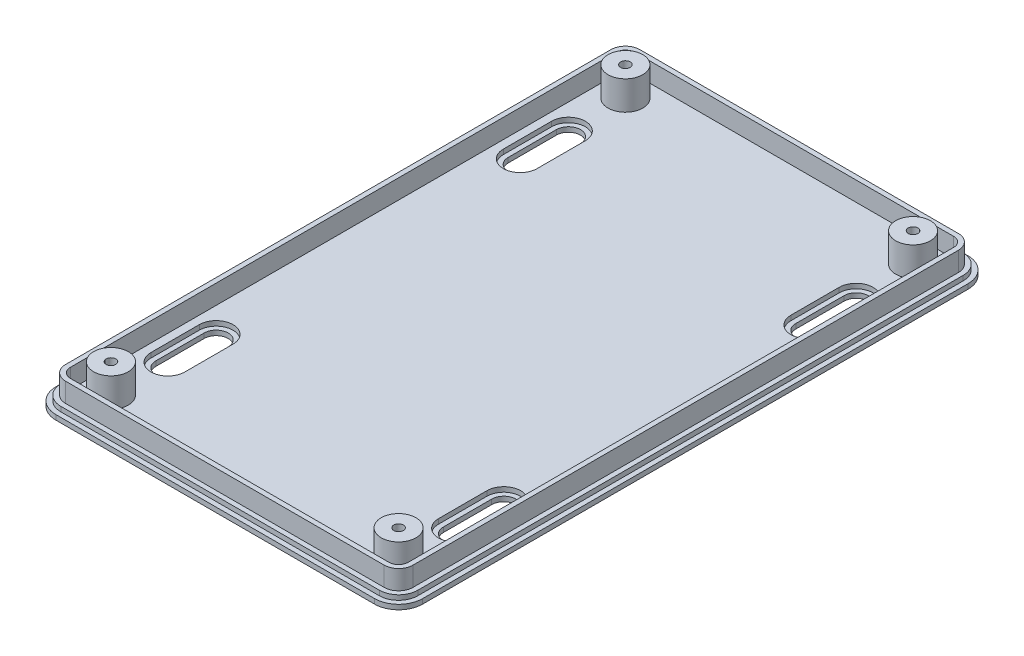
SolidWorks part; units mm, degrees
material "ABS"
ref_plane "Front Plane" through (0, 0, 0) normal (0, 0, 1) x (1, 0, 0)
ref_plane "Top Plane" through (0, 0, 0) normal (0, 1, 0) x (1, 0, 0)
ref_plane "Right Plane" through (0, 0, 0) normal (1, 0, 0) x (0, 0, -1)
sketch "Sketch1" plane through (0, 0, 0) normal (0, 1, 0) x (1, 0, 0)
  line L1 (-33, -56.5) -> (33, -56.5) construction
  line L2 (-33, -56.5) -> (-33, 56.5) construction
  line L3 (-33, 56.5) -> (33, 56.5) construction
  line L4 (33, -56.5) -> (33, 56.5) construction
  line L5 (-33, -56.5) -> (33, 56.5) construction
  line L6 (-33, 56.5) -> (33, -56.5) construction
  line L7 (-38, -61.5) -> (38, -61.5)
  line L8 (-38, -61.5) -> (-38, 61.5)
  line L9 (-38, 61.5) -> (38, 61.5)
  line L10 (38, -61.5) -> (38, 61.5)
  line L11 (-38, -61.5) -> (38, 61.5) construction
  line L12 (-38, 61.5) -> (38, -61.5) construction
  circle A0 centre (-29.8, 53.3) radius 3.6
  circle A1 centre (29.8, 53.3) radius 3.6
  circle A2 centre (29.8, -53.3) radius 3.6
  circle A3 centre (-29.8, -53.3) radius 3.6
  point P0 (0, 0)
  point P14 (0, 0)
  dimension "D5" = 7.2
  dimension "D6" = 7.2
  dimension "D7" = 7.2
  dimension "D8" = 7.2
  dimension "D1" = 66
  dimension "D2" = 113
  dimension "D3" = 3.2
  dimension "D4" = 3.2
  dimension "D9" = 3.2
  dimension "D10" = 3.2
  dimension "D11" = 3.2
  dimension "D12" = 3.2
  dimension "D13" = 3.2
  dimension "D14" = 3.2
  dimension "D15" = 5
  dimension "D16" = 5
extrude "Boss-Extrude2" add sketch "Sketch1" against normal blind 2 contours A3 | L7 L10 L9 L8 A3 A2 A1 A0 | A2 | A0 | A1 | A3 | L8 L7 L10 L9 region at (0, 0, 0) region at (-29.8, 0, -53.3) region at (29.8, 0, -53.3) region at (29.8, 0, 53.3) region at (-29.8, 0, 53.3)
extrude "Boss-Extrude3" add sketch "Sketch1<4>" along normal blind 6 contours A3 | A2 | A0 | A1 region at (-29.8, 0, -53.3) region at (29.8, 0, -53.3) region at (29.8, 0, 53.3) region at (-29.8, 0, 53.3)
sketch "Sketch1<4>" plane through (0, 0, 0) normal (0, 1, 0) x (1, 0, 0) same geometry as "Sketch1"
fillet "Fillet1" radius 5 4 edges at (-38, -1, -61.5) (38, -1, -61.5) (38, -1, 61.5) (-38, -1, 61.5)
sketch "Sketch2" plane through (0, 0, 0) normal (0, 1, 0) x (1, 0, 0)
  line L0 (-29.8, 41.5) -> (-29.8, 31.5) construction
  line L1 (-27.3, 41.5) -> (-27.3, 31.5)
  line L2 (-32.3, 41.5) -> (-32.3, 31.5)
  line L3 (-38, -56.5) -> (-38, 56.5) construction
  line L4 (-33, 61.5) -> (33, 61.5) construction
  line L5 (0, 0) -> (0, 31.5) construction
  line L6 (0, 0) -> (35.6164, 0) construction
  line L7 (29.8, 41.5) -> (29.8, 31.5) construction
  line L8 (27.3, 41.5) -> (27.3, 31.5)
  line L9 (32.3, 41.5) -> (32.3, 31.5)
  line L10 (-29.8, -41.5) -> (-29.8, -31.5) construction
  line L11 (-27.3, -41.5) -> (-27.3, -31.5)
  line L12 (-32.3, -41.5) -> (-32.3, -31.5)
  line L13 (29.8, -41.5) -> (29.8, -31.5) construction
  line L14 (27.3, -41.5) -> (27.3, -31.5)
  line L15 (32.3, -41.5) -> (32.3, -31.5)
  arc A0 (-27.3, 41.5) -> (-32.3, 41.5) centre (-29.8, 41.5) ccw
  arc A1 (-32.3, 31.5) -> (-27.3, 31.5) centre (-29.8, 31.5) ccw
  arc A2 (27.3, 41.5) -> (32.3, 41.5) centre (29.8, 41.5) cw
  arc A3 (32.3, 31.5) -> (27.3, 31.5) centre (29.8, 31.5) cw
  arc A4 (-27.3, -41.5) -> (-32.3, -41.5) centre (-29.8, -41.5) cw
  arc A5 (-32.3, -31.5) -> (-27.3, -31.5) centre (-29.8, -31.5) cw
  arc A6 (27.3, -41.5) -> (32.3, -41.5) centre (29.8, -41.5) ccw
  arc A7 (32.3, -31.5) -> (27.3, -31.5) centre (29.8, -31.5) ccw
  point P2 (-29.8, 36.5)
  point P17 (29.8, 36.5)
  point P24 (-29.8, -36.5)
  point P31 (29.8, -36.5)
  dimension "D1" = 2.5
  dimension "D2" = 10
  dimension "D3" = 8.2
  dimension "D4" = 20
extrude "Cut-Extrude1" cut sketch "Sketch2" against normal through all
sketch "Sketch3" plane through (0, 6, 0) normal (0, 1, 0) x (1, 0, 0)
  line L0 (0, 0) -> (0, -21.6233) construction
  line L1 (0, 0) -> (38, 0) construction
  line L2 (38, -56.5) -> (38, 56.5) construction
  circle A0 centre (-29.8, -53.3) radius 1
  circle A1 centre (29.8, -53.3) radius 1
  circle A2 centre (29.8, 53.3) radius 1
  circle A3 centre (-29.8, 53.3) radius 1
  dimension "D1" = 2
extrude "Cut-Extrude2" cut sketch "Sketch3" against normal through all
sketch "Sketch4" plane through (0, 0, 0) normal (0, 1, 0) x (1, 0, 0)
  line L0 (-33, -61.5) -> (33, -61.5) construction
  line L1 (-38, -56.5) -> (-38, 56.5) construction
  line L2 (-33, 61.5) -> (33, 61.5) construction
  line L3 (38, -56.5) -> (38, 56.5) construction
  line L4 (-33, -61.5) -> (33, -61.5)
  line L5 (-38, -56.5) -> (-38, 56.5)
  line L6 (-33, 61.5) -> (33, 61.5)
  line L7 (38, -56.5) -> (38, 56.5)
  line L8 (-33, -60.5) -> (33, -60.5)
  line L9 (37, -56.5) -> (37, 56.5)
  line L10 (-33, 60.5) -> (33, 60.5)
  line L11 (-37, -56.5) -> (-37, 56.5)
  line L12 (27.3, -31.5) -> (27.3, -41.5) construction
  line L13 (32.3, -41.5) -> (32.3, -31.5) construction
  line L14 (-27.3, -41.5) -> (-27.3, -31.5) construction
  line L15 (-32.3, -31.5) -> (-32.3, -41.5) construction
  line L16 (-32.3, 41.5) -> (-32.3, 31.5) construction
  line L17 (-27.3, 31.5) -> (-27.3, 41.5) construction
  line L18 (27.3, 41.5) -> (27.3, 31.5) construction
  line L19 (32.3, 31.5) -> (32.3, 41.5) construction
  line L20 (32.3, 31.5) -> (32.3, 41.5)
  line L21 (27.3, 41.5) -> (27.3, 31.5)
  line L22 (-27.3, 31.5) -> (-27.3, 41.5)
  line L23 (-32.3, 41.5) -> (-32.3, 31.5)
  line L24 (-32.3, -31.5) -> (-32.3, -41.5)
  line L25 (-27.3, -41.5) -> (-27.3, -31.5)
  line L26 (32.3, -41.5) -> (32.3, -31.5)
  line L27 (27.3, -31.5) -> (27.3, -41.5)
  line L28 (33.3, 31.5) -> (33.3, 41.5)
  line L29 (26.3, 41.5) -> (26.3, 31.5)
  line L30 (-26.3, 31.5) -> (-26.3, 41.5)
  line L31 (-33.3, 41.5) -> (-33.3, 31.5)
  line L32 (-33.3, -31.5) -> (-33.3, -41.5)
  line L33 (-26.3, -41.5) -> (-26.3, -31.5)
  line L34 (33.3, -41.5) -> (33.3, -31.5)
  line L35 (26.3, -31.5) -> (26.3, -41.5)
  arc A0 (33, -61.5) -> (38, -56.5) centre (33, -56.5) ccw construction
  arc A1 (-38, -56.5) -> (-33, -61.5) centre (-33, -56.5) ccw construction
  arc A2 (-33, 61.5) -> (-38, 56.5) centre (-33, 56.5) ccw construction
  arc A3 (38, 56.5) -> (33, 61.5) centre (33, 56.5) ccw construction
  arc A4 (33, -61.5) -> (38, -56.5) centre (33, -56.5) ccw
  arc A5 (-38, -56.5) -> (-33, -61.5) centre (-33, -56.5) ccw
  arc A6 (-33, 61.5) -> (-38, 56.5) centre (-33, 56.5) ccw
  arc A7 (38, 56.5) -> (33, 61.5) centre (33, 56.5) ccw
  arc A8 (33, -60.5) -> (37, -56.5) centre (33, -56.5) ccw
  arc A9 (37, 56.5) -> (33, 60.5) centre (33, 56.5) ccw
  arc A10 (-33, 60.5) -> (-37, 56.5) centre (-33, 56.5) ccw
  arc A11 (-37, -56.5) -> (-33, -60.5) centre (-33, -56.5) ccw
  arc A12 (32.3, -31.5) -> (27.3, -31.5) centre (29.8, -31.5) ccw construction
  arc A13 (27.3, -41.5) -> (32.3, -41.5) centre (29.8, -41.5) ccw construction
  arc A14 (-32.3, -41.5) -> (-27.3, -41.5) centre (-29.8, -41.5) ccw construction
  arc A15 (-27.3, -31.5) -> (-32.3, -31.5) centre (-29.8, -31.5) ccw construction
  arc A16 (-32.3, 31.5) -> (-27.3, 31.5) centre (-29.8, 31.5) ccw construction
  arc A17 (-27.3, 41.5) -> (-32.3, 41.5) centre (-29.8, 41.5) ccw construction
  arc A18 (32.3, 41.5) -> (27.3, 41.5) centre (29.8, 41.5) ccw construction
  arc A19 (27.3, 31.5) -> (32.3, 31.5) centre (29.8, 31.5) ccw construction
  arc A20 (27.3, 31.5) -> (32.3, 31.5) centre (29.8, 31.5) ccw
  arc A21 (32.3, 41.5) -> (27.3, 41.5) centre (29.8, 41.5) ccw
  arc A22 (-27.3, 41.5) -> (-32.3, 41.5) centre (-29.8, 41.5) ccw
  arc A23 (-32.3, 31.5) -> (-27.3, 31.5) centre (-29.8, 31.5) ccw
  arc A24 (-27.3, -31.5) -> (-32.3, -31.5) centre (-29.8, -31.5) ccw
  arc A25 (-32.3, -41.5) -> (-27.3, -41.5) centre (-29.8, -41.5) ccw
  arc A26 (27.3, -41.5) -> (32.3, -41.5) centre (29.8, -41.5) ccw
  arc A27 (32.3, -31.5) -> (27.3, -31.5) centre (29.8, -31.5) ccw
  arc A28 (26.3, 31.5) -> (33.3, 31.5) centre (29.8, 31.5) ccw
  arc A29 (33.3, 41.5) -> (26.3, 41.5) centre (29.8, 41.5) ccw
  arc A30 (-26.3, 41.5) -> (-33.3, 41.5) centre (-29.8, 41.5) ccw
  arc A31 (-33.3, 31.5) -> (-26.3, 31.5) centre (-29.8, 31.5) ccw
  arc A32 (-26.3, -31.5) -> (-33.3, -31.5) centre (-29.8, -31.5) ccw
  arc A33 (-33.3, -41.5) -> (-26.3, -41.5) centre (-29.8, -41.5) ccw
  arc A34 (26.3, -41.5) -> (33.3, -41.5) centre (29.8, -41.5) ccw
  arc A35 (33.3, -31.5) -> (26.3, -31.5) centre (29.8, -31.5) ccw
  arc M17 (27.3, 41.5) -> (32.3, 41.5) centre (29.8, 41.5) cw
  line M18 (32.3, 41.5) -> (32.3, 31.5)
  arc M19 (32.3, 31.5) -> (27.3, 31.5) centre (29.8, 31.5) cw
  line M20 (27.3, 31.5) -> (27.3, 41.5)
  arc M21 (-27.3, -41.5) -> (-32.3, -41.5) centre (-29.8, -41.5) cw
  line M22 (-32.3, -41.5) -> (-32.3, -31.5)
  arc M23 (-32.3, -31.5) -> (-27.3, -31.5) centre (-29.8, -31.5) cw
  line M24 (-27.3, -31.5) -> (-27.3, -41.5)
  arc M25 (32.3, -41.5) -> (27.3, -41.5) centre (29.8, -41.5) cw
  line M26 (27.3, -41.5) -> (27.3, -31.5)
  arc M27 (27.3, -31.5) -> (32.3, -31.5) centre (29.8, -31.5) cw
  line M28 (32.3, -31.5) -> (32.3, -41.5)
  arc M29 (-32.3, 41.5) -> (-27.3, 41.5) centre (-29.8, 41.5) cw
  line M30 (-27.3, 41.5) -> (-27.3, 31.5)
  arc M31 (-27.3, 31.5) -> (-32.3, 31.5) centre (-29.8, 31.5) cw
  line M32 (-32.3, 31.5) -> (-32.3, 41.5)
  line M37 (33, 61.5) -> (-33, 61.5)
  arc M38 (-33, 61.5) -> (-38, 56.5) centre (-33, 56.5) ccw
  line M39 (-38, 56.5) -> (-38, -56.5)
  arc M40 (-38, -56.5) -> (-33, -61.5) centre (-33, -56.5) ccw
  line M41 (-33, -61.5) -> (33, -61.5)
  arc M42 (33, -61.5) -> (38, -56.5) centre (33, -56.5) ccw
  line M43 (38, -56.5) -> (38, 56.5)
  arc M44 (38, 56.5) -> (33, 61.5) centre (33, 56.5) ccw
  dimension "D1" = 1
  dimension "D2" = 1
  dimension "D3" = 1
  dimension "D4" = 1
  dimension "D5" = 1
extrude "Cut-Extrude4" cut sketch "Sketch4" against normal blind 1 contours A11 L11 A10 L10 A9 L9 A8 L8 M44 M37 M38 M39 M40 M41 M42 M43 | L32 A33 L33 A32 M24 M21 M22 M23 | L34 A35 L35 A34 M28 M25 M26 M27 | L28 A29 L29 A28 M20 M17 M18 M19 | L31 A31 L30 A30 M32 M29 M30 M31 region at (-36.4333, 0, 59.9333) region at (29.8, 0, -28.1838) region at (-29.8, 0, -28.1838) region at (-29.8, 0, 28.1838) region at (29.8, 0, 44.8162)
sketch "Sketch5" plane through (0, 0, 0) normal (0, 1, 0) x (1, 0, 0)
  line L0 (-36, 56.5) -> (-36, -56.5)
  line L1 (-33, -59.5) -> (33, -59.5)
  line L2 (36, -56.5) -> (36, 56.5)
  line L3 (33, 59.5) -> (-33, 59.5)
  line L4 (-37, 56.5) -> (-37, -56.5)
  line L5 (-33, -60.5) -> (33, -60.5)
  line L6 (37, -56.5) -> (37, 56.5)
  line L7 (33, 60.5) -> (-33, 60.5)
  line L8 (-37, 56.5) -> (-37, -56.5) construction
  line L9 (-33, -60.5) -> (33, -60.5) construction
  line L10 (37, -56.5) -> (37, 56.5) construction
  line L11 (33, 60.5) -> (-33, 60.5) construction
  line L12 (-35, 56.5) -> (-35, -56.5)
  line L13 (-33, -58.5) -> (33, -58.5)
  line L14 (35, -56.5) -> (35, 56.5)
  line L15 (33, 58.5) -> (-33, 58.5)
  arc A0 (-36, -56.5) -> (-33, -59.5) centre (-33, -56.5) ccw
  arc A1 (33, -59.5) -> (36, -56.5) centre (33, -56.5) ccw
  arc A2 (36, 56.5) -> (33, 59.5) centre (33, 56.5) ccw
  arc A3 (-33, 59.5) -> (-36, 56.5) centre (-33, 56.5) ccw
  arc A4 (-37, -56.5) -> (-33, -60.5) centre (-33, -56.5) ccw
  arc A5 (33, -60.5) -> (37, -56.5) centre (33, -56.5) ccw
  arc A6 (37, 56.5) -> (33, 60.5) centre (33, 56.5) ccw
  arc A7 (-33, 60.5) -> (-37, 56.5) centre (-33, 56.5) ccw
  arc A8 (-37, -56.5) -> (-33, -60.5) centre (-33, -56.5) ccw construction
  arc A9 (33, -60.5) -> (37, -56.5) centre (33, -56.5) ccw construction
  arc A10 (37, 56.5) -> (33, 60.5) centre (33, 56.5) ccw construction
  arc A11 (-33, 60.5) -> (-37, 56.5) centre (-33, 56.5) ccw construction
  arc A12 (-35, -56.5) -> (-33, -58.5) centre (-33, -56.5) ccw
  arc A13 (33, -58.5) -> (35, -56.5) centre (33, -56.5) ccw
  arc A14 (35, 56.5) -> (33, 58.5) centre (33, 56.5) ccw
  arc A15 (-33, 58.5) -> (-35, 56.5) centre (-33, 56.5) ccw
  dimension "D1" = 0
  dimension "D2" = 1
  dimension "D3" = 1
extrude "Boss-Extrude4" add sketch "Sketch5" along normal blind 4
equation "\"D8@Sketch1\"=\"D5@Sketch1\""
equation "\"D6@Sketch1\"=\"D5@Sketch1\""
equation "\"D7@Sketch1\"=\"D5@Sketch1\""
